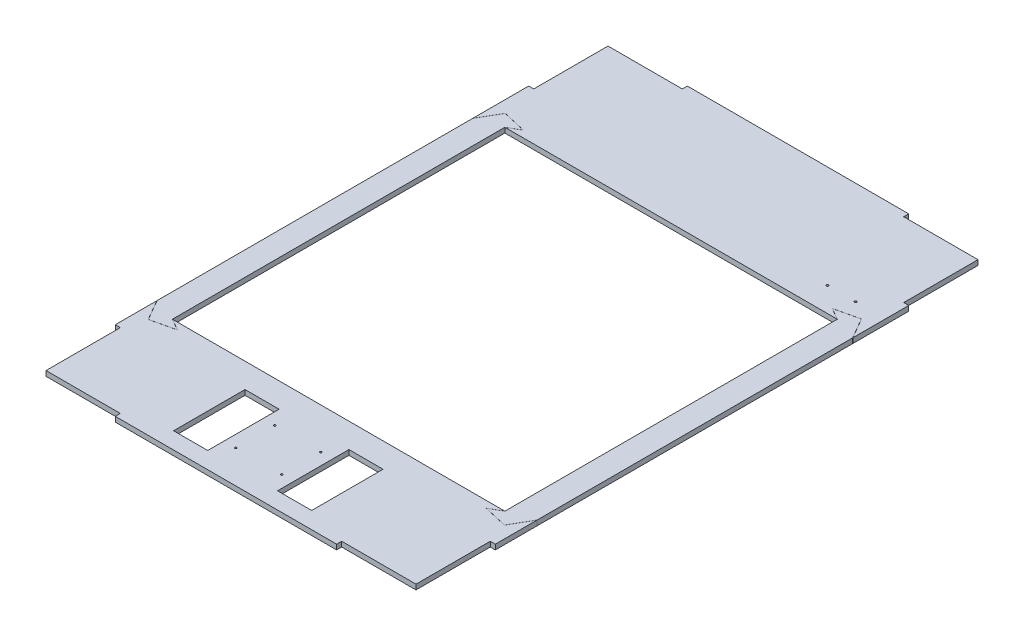
SolidWorks part; units mm, degrees
ref_plane "Front Plane" through (0, 0, 0) normal (0, 0, 1) x (1, 0, 0)
ref_plane "Top Plane" through (0, 0, 0) normal (0, 1, 0) x (1, 0, 0)
ref_plane "Right Plane" through (0, 0, 0) normal (1, 0, 0) x (0, 0, -1)
sketch "Sketch1" plane through (0, 0, 0) normal (0, 1, 0) x (1, 0, 0)
  line L0 (44, -285.5) -> (-44, -285.5) construction
  line L1 (-209.5, -209.5) -> (209.5, -209.5)
  line L2 (-209.5, -209.5) -> (-209.5, 209.5)
  line L3 (-209.5, 209.5) -> (209.5, 209.5)
  line L4 (209.5, -209.5) -> (209.5, 209.5)
  line L5 (-209.5, -209.5) -> (209.5, 209.5) construction
  line L6 (-209.5, 209.5) -> (209.5, -209.5) construction
  line L7 (-239.5, -351.5) -> (239.5, -351.5)
  line L8 (-239.5, -351.5) -> (-239.5, 369.5)
  line L9 (-239.5, 369.5) -> (239.5, 369.5)
  line L10 (239.5, -351.5) -> (239.5, 369.5)
  line L11 (-97, -340.5) -> (97, -340.5) construction
  line L12 (-97, -340.5) -> (-97, -230.5) construction
  line L13 (-97, -230.5) -> (97, -230.5) construction
  line L14 (97, -340.5) -> (97, -230.5) construction
  line L15 (-97, -340.5) -> (97, -230.5) construction
  line L16 (-97, -230.5) -> (97, -340.5) construction
  line L21 (29, -310) -> (-29, -310) construction
  line L22 (29, -310) -> (29, -261) construction
  line L23 (29, -261) -> (-29, -261) construction
  line L24 (-29, -310) -> (-29, -261) construction
  line L25 (29, -310) -> (-29, -261) construction
  line L26 (29, -261) -> (-29, -310) construction
  line L27 (-44, -330.5) -> (-87, -330.5)
  line L28 (-44, -330.5) -> (-44, -240.5)
  line L29 (-44, -240.5) -> (-87, -240.5)
  line L30 (-87, -330.5) -> (-87, -240.5)
  line L31 (87, -330.5) -> (44, -330.5)
  line L32 (87, -330.5) -> (87, -240.5)
  line L33 (87, -240.5) -> (44, -240.5)
  line L34 (44, -330.5) -> (44, -240.5)
  circle A0 centre (-29, -310) radius 1.25
  circle A1 centre (-29, -261) radius 1.25
  circle A2 centre (29, -261) radius 1.25
  circle A3 centre (29, -310) radius 1.25
  point P0 (0, 0)
  point P6 (0, 0)
  point P11 (0, -351.5)
  point P12 (0, -285.5)
  point P17 (0, -285.5)
  point P18 (0, -285.5)
  dimension "D10" = 2.5
  dimension "D1" = 419
  dimension "D2" = 30
  dimension "D3" = 11
  dimension "D4" = 160
  dimension "D5" = 194
  dimension "D6" = 110
  dimension "D7" = 21
  dimension "D8" = 58
  dimension "D9" = 49
  dimension "D11" = 10
  dimension "D12" = 15
  dimension "D13" = 10
extrude "Boss-Extrude1" add sketch "Sketch1" along normal mid plane 6.35
sketch "Sketch2" plane through (0, 3.175, 0) normal (0, 1, 0) x (1, 0, 0)
  line L0 (-239.5, 369.5) -> (-239.5, 269.5)
  line L1 (-239.5, 369.5) -> (-239.5, -351.5) construction
  line L2 (-239.5, 269.5) -> (-233.15, 269.5)
  line L3 (-233.15, 269.5) -> (-233.15, 363.15)
  line L4 (-233.15, 363.15) -> (-139.5, 363.15)
  line L5 (-139.5, 363.15) -> (-139.5, 369.5)
  line L6 (239.5, 369.5) -> (-239.5, 369.5) construction
  line L7 (-139.5, 369.5) -> (-239.5, 369.5)
  line L8 (239.5, 369.5) -> (139.5, 369.5)
  line L9 (139.5, 369.5) -> (139.5, 363.15)
  line L10 (139.5, 363.15) -> (233.15, 363.15)
  line L11 (233.15, 363.15) -> (233.15, 269.5)
  line L12 (233.15, 269.5) -> (239.5, 269.5)
  line L13 (239.5, -351.5) -> (239.5, 369.5) construction
  line L14 (239.5, 269.5) -> (239.5, 369.5)
  line L15 (239.5, -351.5) -> (239.5, -251.5)
  line L16 (239.5, -251.5) -> (233.15, -251.5)
  line L17 (233.15, -251.5) -> (233.15, -345.15)
  line L18 (233.15, -345.15) -> (139.5, -345.15)
  line L19 (139.5, -345.15) -> (139.5, -351.5)
  line L20 (-239.5, -351.5) -> (239.5, -351.5) construction
  line L21 (139.5, -351.5) -> (239.5, -351.5)
  line L22 (-239.5, -351.5) -> (-139.5, -351.5)
  line L23 (-139.5, -351.5) -> (-139.5, -345.15)
  line L24 (-139.5, -345.15) -> (-233.15, -345.15)
  line L25 (-233.15, -345.15) -> (-233.15, -251.5)
  line L26 (-233.15, -251.5) -> (-239.5, -251.5)
  line L27 (-239.5, -251.5) -> (-239.5, -351.5)
  dimension "D1" = 100
  dimension "D2" = 6.35
extrude "Cut-Extrude1" cut sketch "Sketch2" against normal through all
sketch "Sketch3" plane through (0, 3.175, 0) normal (0, 1, 0) x (1, 0, 0)
  line L0 (201.88, 240.12) -> (166.32, 240.12) construction
  line L2 (209.5, 209.5) -> (-209.5, 209.5) construction
  line L3 (161.24, 232.5) -> (209.5, 232.5) construction
  line L4 (161.24, 232.5) -> (161.24, 268.06) construction
  line L5 (161.24, 268.06) -> (209.5, 268.06) construction
  line L6 (209.5, 232.5) -> (209.5, 268.06) construction
  line L7 (209.5, -209.5) -> (209.5, 209.5) construction
  circle A0 centre (166.32, 240.12) radius 1.375
  circle A1 centre (201.88, 240.12) radius 1.375
  dimension "D2" = 2.75
  dimension "D1" = 35.56
  dimension "D3" = 35.56
  dimension "D4" = 48.26
  dimension "D5" = 40.64
  dimension "D6" = 27.94
  dimension "D7" = 23
extrude "Cut-Extrude2" cut sketch "Sketch3" against normal through all
sketch "Sketch4" plane through (0, 3.175, 0) normal (0, 1, 0) x (1, 0, 0)
  line L0 (-209.5, -209.5) -> (-194.7696, -218.0046)
  line L1 (-194.7696, -218.0046) -> (-224.4504, -224.8859)
  line L2 (-224.4504, -224.8859) -> (-239.5, -198.8192)
  line L3 (-239.5, 269.5) -> (-239.5, -251.5) construction
  line L4 (-209.5, -209.5) -> (209.5, -209.5) construction
  line L5 (-239.5, -198.8192) -> (-239.5, -199.0192)
  line L6 (-239.5, -199.0192) -> (-224.5, -225)
  line L7 (-224.5, -225) -> (-194.5, -218.0448)
  line L8 (-194.5, -218.0448) -> (-209.3, -209.5)
  line L9 (-209.3, -209.5) -> (-209.5, -209.5)
  line L10 (-202.1348, -213.7523) -> (-202.0848, -213.6657) construction
  line L11 (-209.61, -221.4452) -> (-209.5874, -221.5427) construction
  line L12 (-231.9752, -211.8525) -> (-232.0618, -211.9025) construction
  line L13 (-3.4925, 0) -> (3.4925, 0) construction
  line L14 (-209.3, 209.5) -> (-209.5, 209.5)
  line L15 (-194.5, 218.0448) -> (-209.3, 209.5)
  line L16 (-224.5, 225) -> (-194.5, 218.0448)
  line L17 (-239.5, 199.0192) -> (-224.5, 225)
  line L18 (-239.5, 198.8192) -> (-239.5, 199.0192)
  line L19 (-224.4504, 224.8859) -> (-239.5, 198.8192)
  line L20 (-194.7696, 218.0046) -> (-224.4504, 224.8859)
  line L21 (-209.5, 209.5) -> (-194.7696, 218.0046)
  line L22 (0, -3.4925) -> (0, 3.4925) construction
  line L23 (194.5, -218.0448) -> (209.3, -209.5)
  line L24 (224.5, -225) -> (194.5, -218.0448)
  line L25 (239.5, -199.0192) -> (224.5, -225)
  line L26 (239.5, -198.8192) -> (239.5, -199.0192)
  line L27 (224.4504, -224.8859) -> (239.5, -198.8192)
  line L28 (194.7696, -218.0046) -> (224.4504, -224.8859)
  line L29 (209.5, -209.5) -> (194.7696, -218.0046)
  line L30 (209.3, -209.5) -> (209.5, -209.5)
  line L31 (194.5, 218.0448) -> (209.3, 209.5)
  line L32 (224.5, 225) -> (194.5, 218.0448)
  line L33 (239.5, 199.0192) -> (224.5, 225)
  line L34 (239.5, 198.8192) -> (239.5, 199.0192)
  line L35 (224.4504, 224.8859) -> (239.5, 198.8192)
  line L36 (194.7696, 218.0046) -> (224.4504, 224.8859)
  line L37 (209.5, 209.5) -> (194.7696, 218.0046)
  line L38 (209.3, 209.5) -> (209.5, 209.5)
  dimension "D1" = 30
  dimension "D2" = 30
  dimension "D3" = 0.1
  dimension "D4" = 450
  dimension "D5" = 15
  dimension "D6" = 15
extrude "Cut-Extrude3" cut sketch "Sketch4" against normal through all
delete or keep bodies "Body-Delete/Keep 1" [suppressed] type keep bodies bodies 104
delete or keep bodies "Body-Delete/Keep 2" [suppressed] type keep bodies bodies 105
delete or keep bodies "Body-Delete/Keep 3" [suppressed] type keep bodies bodies 106
delete or keep bodies "Body-Delete/Keep 4" [suppressed] type keep bodies bodies 107
